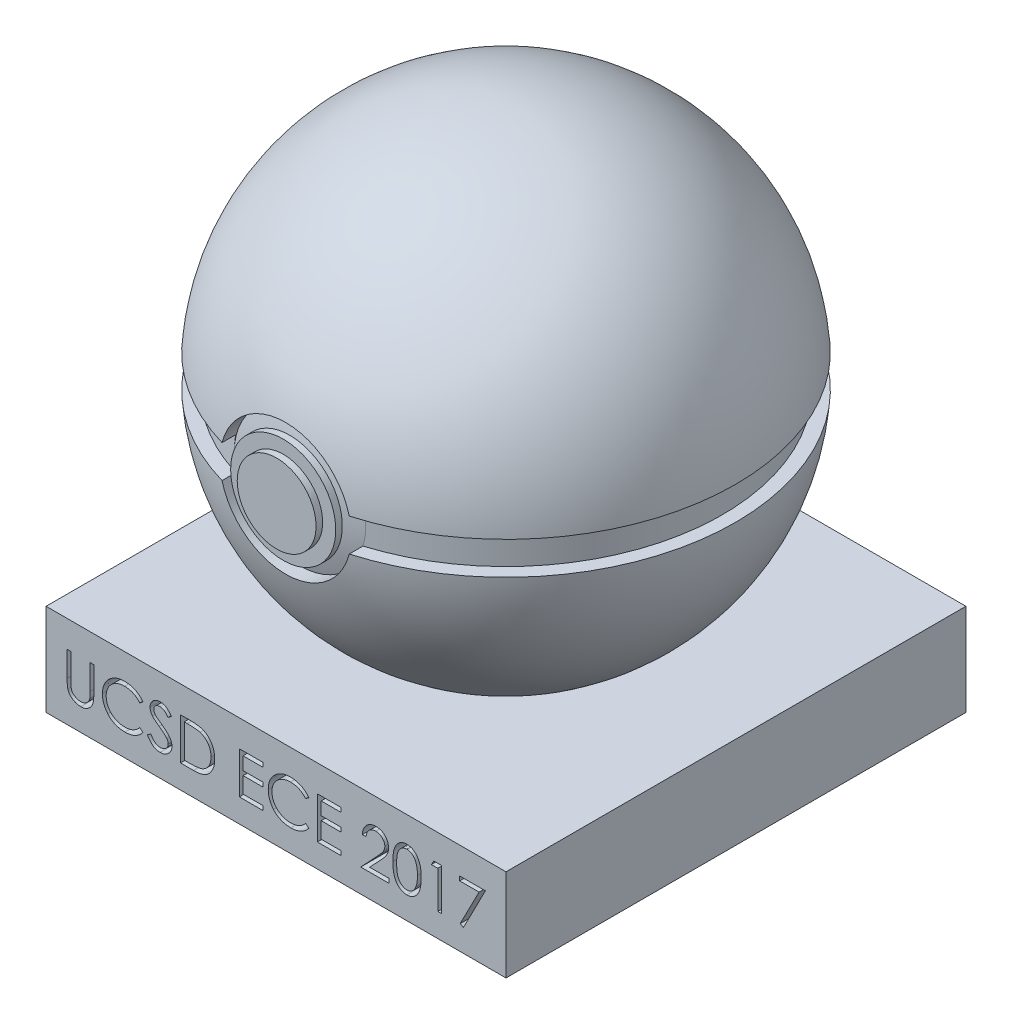
SolidWorks part; units mm, degrees
ref_plane "Front Plane" through (0, 0, 0) normal (0, 0, 1) x (1, 0, 0)
ref_plane "Top Plane" through (0, 0, 0) normal (0, 1, 0) x (1, 0, 0)
ref_plane "Right Plane" through (0, 0, 0) normal (1, 0, 0) x (0, 0, -1)
sketch "Sketch3" plane through (0, 0, 0) normal (0, 0, 1) x (1, 0, 0)
  line L0 (0, 17.5) -> (0, -17.5)
  line L1 (0, 0) -> (-16.4553, 0) construction
  line L3 (-17.4553, 1.25) -> (-16.4553, 1.25)
  line L5 (-17.4553, -1.25) -> (-16.4553, -1.25)
  line L6 (-16.4553, 1.25) -> (-16.4553, -1.25)
  arc A0 (0, 17.5) -> (-17.4553, 1.25) centre (0, 0) ccw
  arc A1 (-17.4553, -1.25) -> (0, -17.5) centre (0, 0) ccw
  dimension "D1" = 35
  dimension "D2" = 2.5
  dimension "D3" = 1
revolve "Revolve1" add sketch "Sketch3" angle 360 about L0
ref_plane "Plane1" through (0, 0, 16.4553) normal (0, 0, -1) x (-1, 0, 0)
sketch "Sketch7" plane through (0, 0, 0) normal (1, 0, 0) x (0, 0, -1)
  line L1 (-15.6773, -5) -> (-36.4553, -5)
  line L3 (0, 0) -> (-9.7313, 0) construction
  line L4 (-36.4553, 0) -> (-36.4553, -5)
  line L5 (-36.4553, 0) -> (-16.4553, 0)
  line L6 (-16.4553, 1.25) -> (-16.4553, -1.25) construction
  line L7 (-16.4553, 1.25) -> (-16.4553, -1.25) construction
  arc A0 (-16.4553, 0) -> (-15.6773, -5) centre (0, 0) ccw
  dimension "D1" = 5
  dimension "D2" = 20
revolve "Cut-Revolve1" cut sketch "Sketch7" angle 360 about L3
ref_plane "Plane2" through (0, -17.5, 0) normal (0, -1, 0) x (-1, 0, 0)
sketch "Sketch8" plane through (0, -17.5, 0) normal (0, -1, 0) x (-1, 0, 0)
  line L1 (-17.5, -17.5) -> (17.5, -17.5)
  line L2 (-17.5, -17.5) -> (-17.5, 17.5)
  line L3 (-17.5, 17.5) -> (17.5, 17.5)
  line L4 (17.5, -17.5) -> (17.5, 17.5)
  line L5 (-17.5, -17.5) -> (17.5, 17.5) construction
  line L6 (-17.5, 17.5) -> (17.5, -17.5) construction
  point P0 (0, 0)
  dimension "D1" = 35
  dimension "D2" = 35
extrude "Boss-Extrude1" add sketch "Sketch8" along normal blind 5 and the other way blind 2 separate body
sketch "Sketch10" plane through (0, 0, 16.4553) normal (0, 0, -1) x (-1, 0, 0)
  circle A0 centre (0, 0) radius 4
  dimension "D1" = 8
extrude "Boss-Extrude2" add sketch "Sketch10" against normal blind 0.5 separate body contours A0
sketch "Sketch11" plane through (0, 0, 16.4553) normal (0, 0, -1) x (-1, 0, 0)
  circle A0 centre (0, 0) radius 3
  dimension "D1" = 6
extrude "Boss-Extrude3" add sketch "Sketch11" against normal blind 1
sketch "Sketch12" plane through (0, 0, 17.5) normal (0, 0, 1) x (1, 0, 0)
  text T0 "UCSD ECE 2017"
extrude "Cut-Extrude1" cut sketch "Sketch12" against normal blind 2
sketch "Sketch14" plane through (0, 0, 0) normal (1, 0, 0) x (0, 0, -1)
  line L0 (8.124, -15.5) -> (-8.124, -15.5)
  line L1 (-17.5, -15.5) -> (17.5, -15.5) construction
  arc A0 (-16.7705, -5) -> (17.4553, -1.25) centre (0, 0) ccw construction
  arc A1 (8.124, -15.5) -> (-8.124, -15.5) centre (0, 0.4657) cw
extrude "Cut-Extrude2" cut sketch "Sketch14" against normal blind 12 and the other way blind 12 body kept at (-8.124, -15.5, 0)
sketch "Sketch16" plane through (0, -22.5, 0) normal (0, -1, 0) x (1, 0, 0)
  text T0 "<b><i>Never stop</i></b>\r\n<b><i>Catching 'em</i></b>\r\n<b><i>              Love,</i></b>\r\n<b><i>              Dad</i></b>"
extrude "Cut-Extrude3" cut sketch "Sketch16" against normal blind 2
sketch "Sketch15" plane through (0, -22.5, 0) normal (0, -1, 0) x (-1, 0, 0)
  text T0 "<b><i>Never stop</i></b>\r\n<b><i>Catching 'em</i></b>\r\n<b><i>            Love,</i></b>\r\n<b><i>            Dad</i></b>"
sketch "Sketch6" [suppressed] plane through (0, 0, 27.5576) normal (0, 0, 1) x (1, 0, 0)
  line L0 (0, 0) -> (0, 0.9309)
  line L1 (-27.5576, 6.3675) -> (27.5576, 6.3675) construction
  line L2 (1.9166, 6.3675) -> (18.0617, 6.3675)
  line L3 (29.3165, -6.3675) -> (-29.3165, -6.3675) construction
  line L4 (17.2906, -6.3675) -> (2.6877, -6.3675)
  arc A0 (0, 0) -> (2.6877, -6.3675) centre (9.9892, 0.4655) ccw
  arc A1 (1.9166, 6.3675) -> (0, 0.9309) centre (9.9892, 0.4655) ccw
  arc A2 (17.2906, -6.3675) -> (18.0617, 6.3675) centre (9.9892, 0.4655) ccw
  dimension "D1" = 20
wrap "Wrap5" [suppressed] sketch "Sketch6" source sketch "Sketch6" thickness 1 parameters "D1"=1
